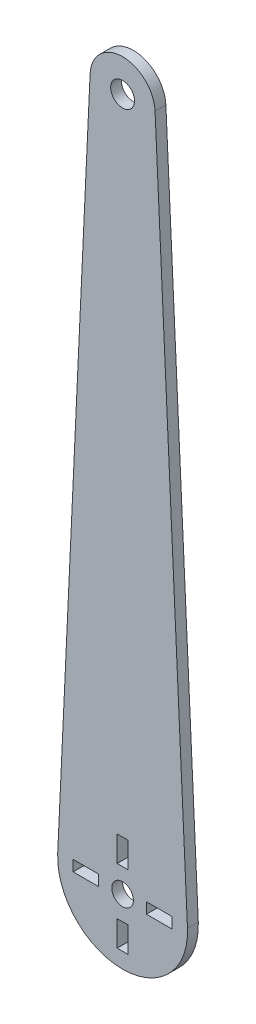
SolidWorks part; units mm, degrees
ref_plane "Front Plane" through (0, 0, 0) normal (0, 0, 1) x (1, 0, 0)
ref_plane "Top Plane" through (0, 0, 0) normal (0, 1, 0) x (1, 0, 0)
ref_plane "Right Plane" through (0, 0, 0) normal (1, 0, 0) x (0, 0, -1)
sketch "Sketch1" plane through (0, 0, 0) normal (0, 0, 1) x (1, 0, 0)
  line L0 (-19.0291, 0.892) -> (-9.525, 203.6465)
  line L1 (19.0291, 0.892) -> (9.525, 203.6465)
  line L2 (-7, 0) -> (0, 0) construction
  line L3 (-1.5875, 7) -> (1.5875, 7)
  line L4 (-1.5875, 7) -> (-1.5875, 14.5)
  line L5 (-1.5875, 14.5) -> (1.5875, 14.5)
  line L6 (1.5875, 7) -> (1.5875, 14.5)
  line L7 (7, 1.5875) -> (14.5, 1.5875)
  line L8 (7, 1.5875) -> (7, -1.5875)
  line L9 (7, -1.5875) -> (14.5, -1.5875)
  line L10 (14.5, 1.5875) -> (14.5, -1.5875)
  line L11 (-1.5875, -7) -> (1.5875, -7)
  line L12 (-1.5875, -7) -> (-1.5875, -14.5)
  line L13 (-1.5875, -14.5) -> (1.5875, -14.5)
  line L14 (1.5875, -7) -> (1.5875, -14.5)
  line L15 (-14.5, 1.5875) -> (-7, 1.5875)
  line L16 (-14.5, 1.5875) -> (-14.5, -1.5875)
  line L17 (-14.5, -1.5875) -> (-7, -1.5875)
  line L18 (-7, 1.5875) -> (-7, -1.5875)
  line L19 (0, 0) -> (0, 7) construction
  line L20 (0, -7) -> (0, 0) construction
  line L21 (0, 0) -> (7, 0) construction
  circle A0 centre (0, 0) radius 3.175
  arc A1 (19.0291, 0.892) -> (-19.0291, 0.892) centre (0, 0) cw
  arc A2 (-9.525, 203.6465) -> (9.525, 203.6465) centre (0, 203.2) cw
  circle A3 centre (0, 203.2) radius 3.5
  point P25 (0, 7)
  point P26 (7, 0)
  dimension "D1" = 6.35
  dimension "D2" = 19.05
  dimension "D5" = 7
  dimension "D3" = 19.05
  dimension "D4" = 203.2
  dimension "D6" = 3.175
  dimension "D7" = 7.5
  dimension "D8" = 7
extrude "Boss-Extrude1" add sketch "Sketch1" along normal blind 3.175
